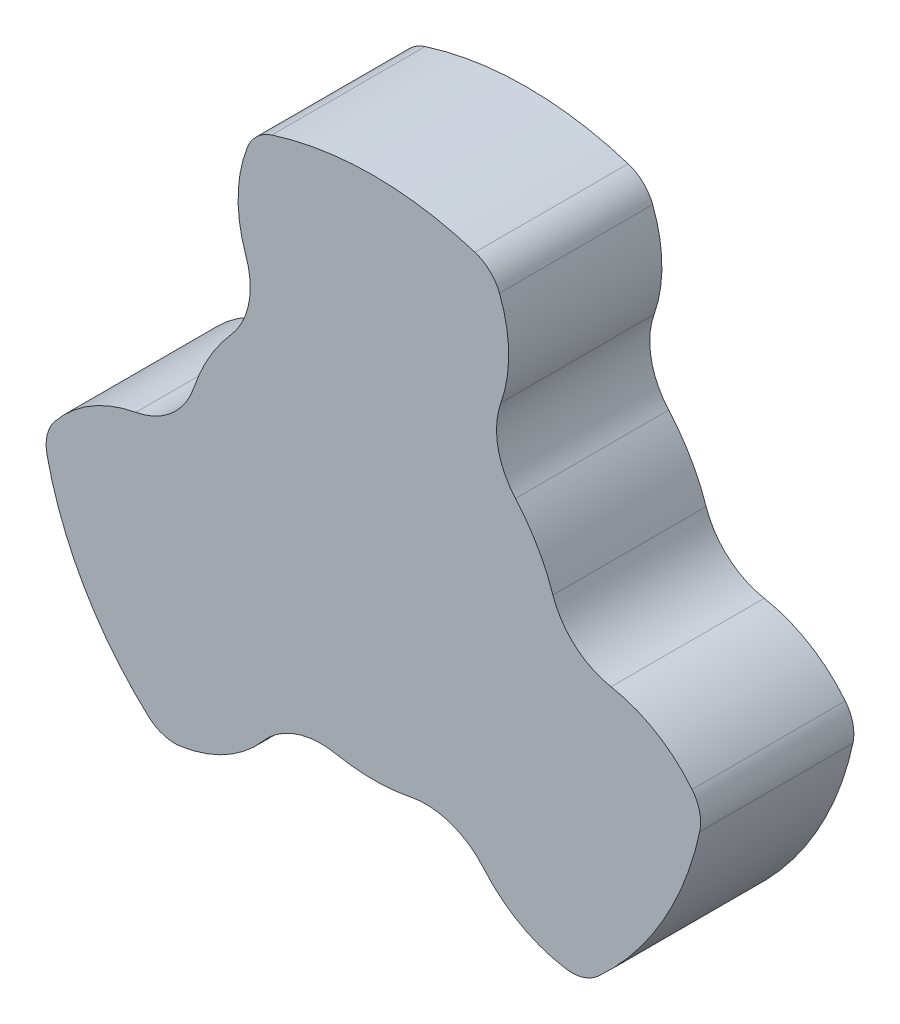
SolidWorks part; units mm, degrees
ref_plane "Front Plane" through (0, 0, 0) normal (0, 0, 1) x (1, 0, 0)
ref_plane "Top Plane" through (0, 0, 0) normal (0, 1, 0) x (1, 0, 0)
ref_plane "Right Plane" through (0, 0, 0) normal (1, 0, 0) x (0, 0, -1)
sketch "Sketch1" plane through (0, 0, 0) normal (0, 0, 1) x (1, 0, 0)
  arc A48 (19.0956, -27.2865) -> (12.381, -31.2996) centre (21.1301, -38.3145) ccw
  arc A49 (12.381, -31.2996) -> (11.7435, -34.0154) centre (14.9076, -33.3254) ccw
  arc A50 (11.7435, -34.0154) -> (20.1599, -48.5931) centre (38.7937, -28.1164) ccw
  arc A51 (20.1599, -48.5931) -> (22.8306, -49.3989) centre (22.3395, -46.1979) ccw
  arc A52 (22.8306, -49.3989) -> (29.6634, -45.5904) centre (21.1301, -38.3145) ccw
  arc A53 (35.6898, -43.5068) -> (29.6634, -45.5904) centre (34.447, -49.6693) ccw
  arc A54 (35.6898, -43.5068) -> (41.8976, -43.5068) centre (38.7937, -28.1164) ccw
  arc A55 (47.9241, -45.5904) -> (41.8976, -43.5068) centre (43.1404, -49.6693) ccw
  arc A56 (47.9241, -45.5904) -> (54.7568, -49.3989) centre (56.4574, -38.3145) ccw
  arc A57 (54.7568, -49.3989) -> (57.4276, -48.5931) centre (55.2479, -46.1979) ccw
  arc A58 (57.4276, -48.5931) -> (65.844, -34.0154) centre (38.7937, -28.1164) ccw
  arc A59 (65.844, -34.0154) -> (65.2065, -31.2996) centre (62.6798, -33.3254) ccw
  arc A60 (65.2065, -31.2996) -> (58.4919, -27.2865) centre (56.4574, -38.3145) ccw
  arc A61 (53.6742, -23.1092) -> (58.4919, -27.2865) centre (59.6324, -21.1043) ccw
  arc A62 (53.6742, -23.1092) -> (50.5703, -17.7331) centre (38.7937, -28.1164) ccw
  arc A63 (49.3615, -11.4722) -> (50.5703, -17.7331) centre (55.2857, -13.5756) ccw
  arc A64 (49.3615, -11.4722) -> (49.2434, -3.6507) centre (38.7937, -7.7202) ccw
  arc A65 (49.2434, -3.6507) -> (47.2101, -1.7407) centre (46.2256, -4.8259) ccw
  arc A66 (47.2101, -1.7407) -> (30.3773, -1.7407) centre (38.7937, -28.1164) ccw
  arc A67 (30.3773, -1.7407) -> (28.3441, -3.6507) centre (31.3618, -4.8259) ccw
  arc A68 (28.3441, -3.6507) -> (28.2259, -11.4722) centre (38.7937, -7.7202) ccw
  arc A69 (27.0172, -17.7331) -> (28.2259, -11.4722) centre (22.3018, -13.5756) ccw
  arc A70 (27.0172, -17.7331) -> (23.9133, -23.1092) centre (38.7937, -28.1164) ccw
  arc A71 (19.0956, -27.2865) -> (23.9133, -23.1092) centre (17.9551, -21.1043) ccw
extrude "Boss-Extrude1" add sketch "Sketch1" along normal blind 12.7 contours A48 A49 A50 A51 A52 A53 A54 A55 A56 A57 A58 A59 A60 A61 A62 A63 A64 A65 A66 A67 A68 A69 A70 A71
